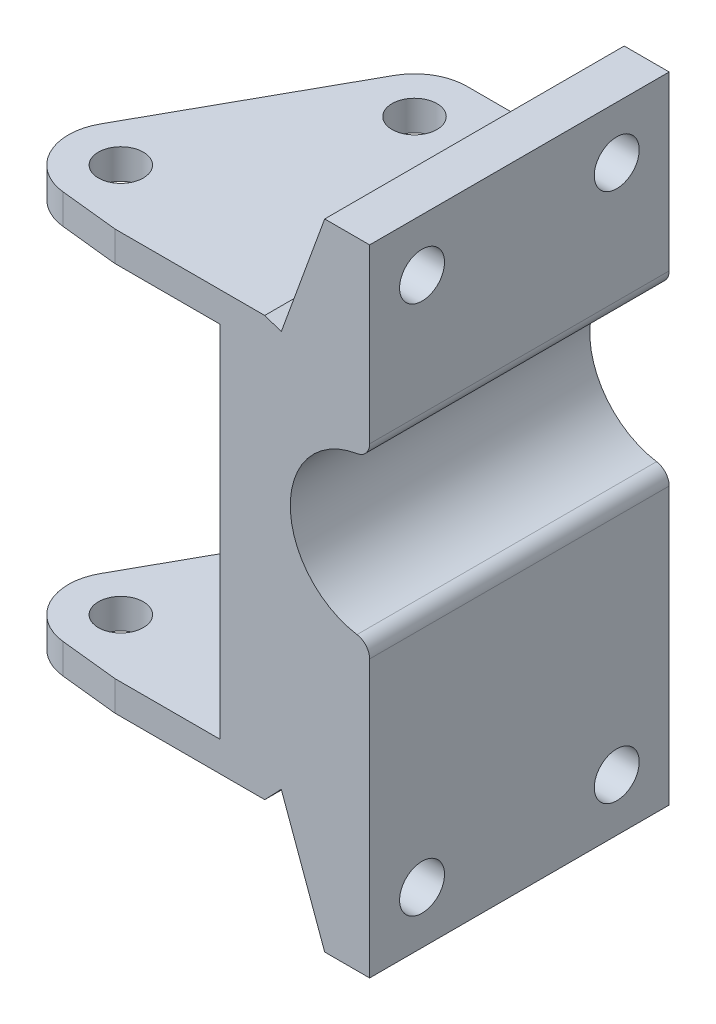
SolidWorks part; units mm, degrees
ref_plane "Front Plane" through (0, 0, 0) normal (0, 0, 1) x (1, 0, 0)
ref_plane "Top Plane" through (0, 0, 0) normal (0, 1, 0) x (1, 0, 0)
ref_plane "Right Plane" through (0, 0, 0) normal (1, 0, 0) x (0, 0, -1)
sketch "Sketch1" plane through (0, 0, 0) normal (0, 0, 1) x (1, 0, 0)
  line L2 (10, -2) -> (17.0032, 5.3081)
  line L3 (10, 26) -> (17.0032, 23.582)
  line L4 (17.0032, 10.5591) -> (17.0032, 5.3081)
  line L5 (17.0032, 21.1591) -> (17.0032, 23.582)
  line L6 (17.0032, 5.3081) -> (22.2738, 10.8083) construction
  line L7 (17.0032, 23.582) -> (19.3857, 22.7593) construction
  line L9 (7, 26) -> (10, 26)
  line L10 (7, 26) -> (7, -2)
  line L11 (7, -2) -> (10, -2)
  line L12 (10, 26) -> (10, -2) construction
  line L13 (-1.4417, 0) -> (5.5583, 0) construction
  line L15 (7, 24) -> (7, 0) construction
  line L16 (7, 24) -> (0, 24) construction
  circle A0 centre (17.0032, 15.8591) radius 5.3 construction
  arc A1 (17.0032, 21.1591) -> (17.0032, 10.5591) centre (17.0032, 15.8591) ccw
  arc A2 (22.2738, 10.8083) -> (19.3857, 22.7593) centre (17.0032, 15.8591) ccw construction
  circle A4 centre (17.0032, 15.8591) radius 7.3 construction
  arc A5 (17.0032, 10.5591) -> (17.0032, 21.1591) centre (17.0032, 15.8591) ccw construction
  circle A6 centre (17.0032, 15.8591) radius 5.3 construction
  point P7 (33.3, 12)
  point P13 (31.0684, 13.5496)
  dimension "D2" = 3
  dimension "D3" = 2
  dimension "D4" = 2
  dimension "D1" = 2
extrude "Boss-Extrude1" add sketch "Sketch1" against normal blind 20
sketch "Sketch2" plane through (0, -2, 0) normal (0, -1, 0) x (1, 0, 0)
  line L1 (0.44, -18.1989) -> (-6.56, -5.5904)
  line L2 (7, -20) -> (3.5, -20)
  line L3 (7, -20) -> (7, 0)
  line L4 (0, 0) -> (-3.8698, -0.4111)
  line L5 (7, 0) -> (0, 0)
  line L6 (-7, 0) -> (7, 0) construction
  line L7 (0, -7.3915) -> (0, 0) construction
  circle A0 centre (-3.5, -3.8915) radius 1.5 construction
  circle A1 centre (3.5, -16.5) radius 1.5 construction
  circle A2 centre (-3.5, -3.8915) radius 1.5
  circle A3 centre (3.5, -16.5) radius 1.5
  arc A4 (-3.8698, -0.4111) -> (-6.56, -5.5904) centre (-3.5, -3.8915) ccw
  arc A5 (0.44, -18.1989) -> (3.5, -20) centre (3.5, -16.5) ccw
  arc A6 (-6.56, -5.5904) -> (-3.8698, -0.4111) centre (-3.5, -3.8915) ccw construction
  arc A7 (7, -16.5) -> (0.44, -18.1989) centre (3.5, -16.5) ccw construction
  arc A8 (3.5, -20) -> (7, -16.5) centre (3.5, -16.5) ccw construction
  dimension "D1" = 2
  dimension "D2" = 2
extrude "Boss-Extrude2" add sketch "Sketch2" against normal blind 2
extrude "Boss-Extrude3" add sketch "Sketch2<2>" along normal blind 2 from surface starting at face at (8.5, 26, -10)
sketch "Sketch2<2>" plane through (0, -2, 0) normal (0, -1, 0) x (1, 0, 0) same geometry as "Sketch2"
sketch "Sketch3" plane through (0, 0, -20) normal (0, 0, -1) x (-1, 0, 0)
  line L0 (-17.0032, 5.3081) -> (-17.0032, -8.8106)
  line L1 (-17.0032, -8.8106) -> (-14.0032, -8.8106)
  line L2 (-14.0032, -8.8106) -> (-11.1047, -0.8472)
  line L3 (-10, -2) -> (-17.0032, 5.3081) construction
  line L4 (-11.1047, -0.8472) -> (-17.0032, 5.3081)
  line L5 (-17.0032, 23.582) -> (-17.0032, 33.582)
  line L6 (-17.0032, 33.582) -> (-14.0032, 33.582)
  line L7 (-14.0032, 33.582) -> (-11.1047, 25.6186)
  line L8 (-17.0032, 23.582) -> (-10, 26) construction
  line L9 (-11.1047, 25.6186) -> (-17.0032, 23.582)
  dimension "D1" = 3
  dimension "D2" = 70
  dimension "D3" = 10
  dimension "D4" = 70
extrude "Boss-Extrude4" add sketch "Sketch3" against normal up to surface (20 mm away) up to face at (8.0594, 13.0507, 0)
fillet "Fillet1" radius 1 rebuild error yes
fillet "Fillet2" radius 1 2 edges at (17.0032, 21.1591, -10) (17.0032, 10.5591, -10)
sketch "Sketch4" plane through (17.0032, 0, 0) normal (1, 0, 0) x (0, 0, -1)
  line L0 (20, 22.0792) -> (20, 33.582) construction
  line L2 (0, 33.582) -> (20, 33.582) construction
  line L3 (0, 22.0792) -> (0, 33.582) construction
  line L4 (0, -8.8106) -> (0, 9.6389) construction
  line L5 (0, -8.8106) -> (20, -8.8106) construction
  circle A0 centre (16.5, -5.3106) radius 1.5
  circle A1 centre (3.5, -5.3106) radius 1.5
  circle A2 centre (16.5, 30.082) radius 1.5
  circle A3 centre (3.5, 30.082) radius 1.5
  circle A4 centre (16.5, 30.082) radius 3.5 construction
  circle A5 centre (16.5, -5.3106) radius 3.5 construction
  circle A6 centre (3.5, -5.3106) radius 3.5 construction
  circle A7 centre (3.5, 30.082) radius 3.5 construction
  dimension "D2" = 3
  dimension "D1" = 2
extrude "Cut-Extrude1" cut sketch "Sketch4" against normal up to next
extrude "Cut-Extrude-Thin2" cut sketch "Sketch4<2>" against normal blind 2 from offset 3 thin offset against normal yes thin type one direction wall 1
sketch "Sketch4<2>" plane through (17.0032, 0, 0) normal (1, 0, 0) x (0, 0, -1) same geometry as "Sketch4"
